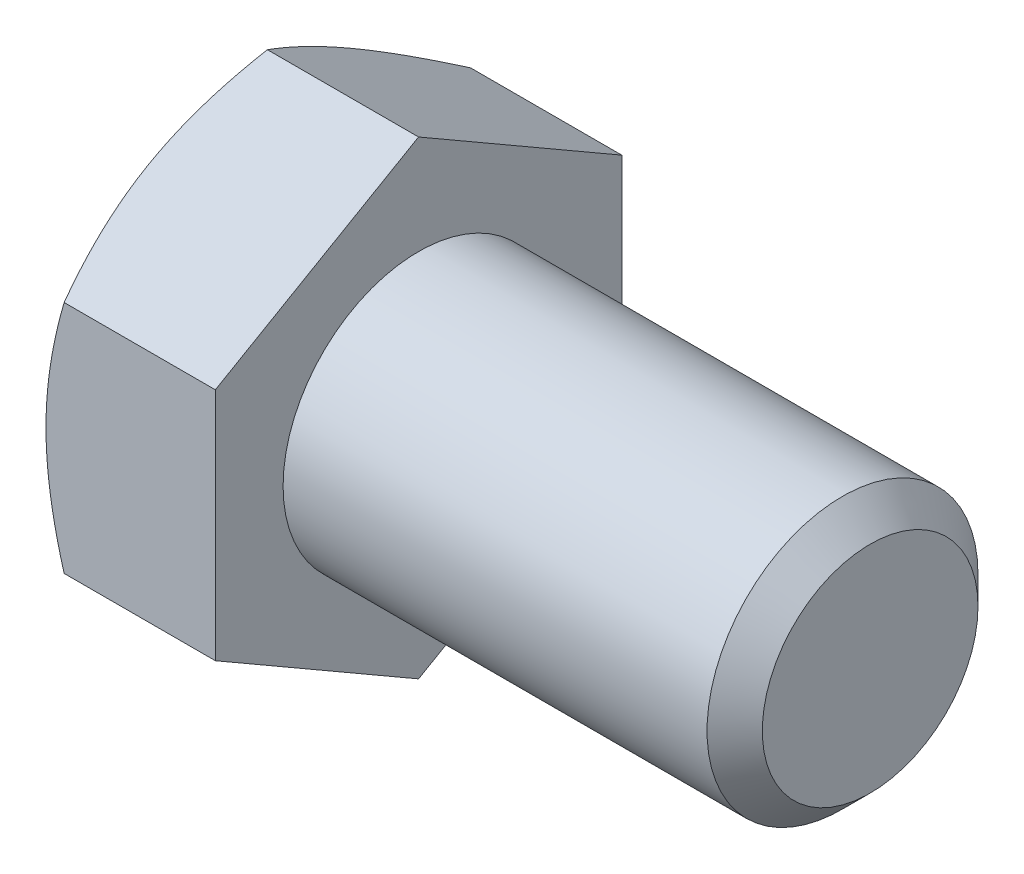
SolidWorks part; units mm, degrees
ref_plane "Front Plane" through (0, 0, 0) normal (0, 0, 1) x (1, 0, 0)
ref_plane "Top Plane" through (0, 0, 0) normal (0, 1, 0) x (1, 0, 0)
ref_plane "Right Plane" through (0, 0, 0) normal (1, 0, 0) x (0, 0, -1)
sketch "Sketch1" plane through (0, 0, 0) normal (0, 0, 1) x (1, 0, 0)
  line L0 (-10.9141, 0) -> (10.9141, 0) construction
  line L1 (10.9141, 4.7625) -> (10.9141, -4.7625) construction
  line L2 (-4.9609, 7.1437) -> (-4.9609, -7.1437) construction
  line L3 (-10.9141, 7.1437) -> (-10.9141, -7.1437) construction
  point P9 (-4.9609, 0)
  point P10 (5.3578, -4.7625)
  dimension "Screw Dia" = 9.525
  dimension "Hex" = 14.2875
  dimension "Head Ht" = 5.9531
  dimension "Screw Lenght" = 15.875
  dimension "D1" = 5.5562
ref_plane "Plane2" through (10.9141, 0, 0) normal (1, 0, 0) x (0, 0, -1)
sketch "Sketch5" plane through (10.9141, 0, 0) normal (1, 0, 0) x (0, 0, -1)
  circle A0 centre (0, 0) radius 4.7625
extrude "Boss-Extrude3" add sketch "Sketch5" against normal up to vertex (15.875 mm away) up to point (-4.9609, 0, 0)
sketch "Sketch9" plane through (10.9141, 0, 0) normal (1, 0, 0) x (0, 0, -1)
  circle A1 centre (0, 0) radius 4.7625
  circle A2 centre (0, 0) radius 4.7625
  dimension "D1" = 0
curve "Helix/Spiral1" pitch 1.5875 height 17.4625 turns 11 parameters "Pitch"=1.5875
chamfer "Chamfer1" distance 0.9715 angle 45 1 edges at (10.9141, 0, -4.7625)
sketch "Sketch10" plane through (0, 0, 0) normal (0, 0, 1) x (1, 0, 0)
  line L0 (10.9141, 4.7625) -> (11.5094, 3.7314)
  line L1 (11.5094, 3.7314) -> (11.7078, 3.7314)
  line L2 (11.7078, 3.7314) -> (12.3031, 4.7625)
  line L3 (10.9141, 4.7625) -> (12.3031, 4.7625)
  line L4 (11.6086, 4.7625) -> (11.6086, 3.7314) construction
  line L5 (11.2117, 4.2469) -> (12.0055, 4.2469) construction
  dimension "D1" = 60
  dimension "D2" = 0.1984
  dimension "D3" = 0.7937
sweep "Cut-Sweep1" [suppressed] cut profiles "Sketch10" path "Helix/Spiral1"
sketch "Sketch6" plane through (-4.9609, 0, 0) normal (-1, 0, 0) x (0, 0, 1)
  line L0 (0, 7.1437) -> (0, -7.1437) construction
  line L1 (7.1437, 4.1244) -> (0, 8.2489)
  line L2 (0, 8.2489) -> (-7.1438, 4.1244)
  line L3 (-7.1438, 4.1244) -> (-7.1438, -4.1244)
  line L4 (-7.1438, -4.1244) -> (0, -8.2489)
  line L5 (0, -8.2489) -> (7.1438, -4.1244)
  line L6 (7.1438, -4.1244) -> (7.1437, 4.1244)
  circle A0 centre (0, 0) radius 7.1438 construction
extrude "Boss-Extrude4" add sketch "Sketch6" along normal up to vertex (5.9531 mm away) up to point (-10.9141, -7.1437, 0)
sketch "Sketch7" plane through (-10.9141, 0, 0) normal (-1, 0, 0) x (0, 0, 1)
  circle A0 centre (0, 0) radius 7.1438 construction
  circle A1 centre (0, 0) radius 7.1438
sketch "Sketch8" plane through (-10.9141, 0, 0) normal (-1, 0, 0) x (0, 0, 1)
  circle A0 centre (0, 0) radius 7.1438 construction
  circle A1 centre (0, 0) radius 7.1438
extrude "Cut-Extrude3" cut sketch "Sketch8" against normal through all draft 60 flip side to cut
sketch "Sketch12" plane through (-10.9141, 0, 0) normal (-1, 0, 0) x (0, 0, 1)
  line L0 (0, 5.5007) -> (0, 3.0718) construction
  line L1 (0.2143, 5.5007) -> (0.2143, 3.0718)
  line L2 (-0.2143, 5.5007) -> (-0.2143, 3.0718)
  line L3 (0, 4.7625) -> (0, -4.7625) construction
  arc A0 (0.2143, 5.5007) -> (-0.2143, 5.5007) centre (0, 5.5007) ccw
  arc A1 (-0.2143, 3.0718) -> (0.2143, 3.0718) centre (0, 3.0718) ccw
  circle A3 centre (0, 0) radius 2.8575 construction
  circle A4 centre (0, 0) radius 5.715 construction
  point P2 (0, 4.2862)
  dimension "D1" = 5.715
  dimension "D3" = 11.43
  dimension "D2" = 0.4286
extrude "Cut-Extrude4" cut sketch "Sketch12" against normal blind 0.254
pattern_circular "CirPattern1" count 3 over 360 about axis through (-4.9609, 0, 0) along (1, 0, 0) of "Cut-Extrude4"
equation "\"D2@Sketch10\" = \"Pitch@Helix/Spiral1\"*.125"
equation "\"D3@Sketch10\" = \"Pitch@Helix/Spiral1\"*.5"
equation "\"D1@Chamfer1\" = \"Pitch@Helix/Spiral1\"*.612"
equation "\"D1@Sketch12\" = \"Hex@Sketch1\"*.4"
equation "\"D3@Sketch12\" = \"Hex@Sketch1\"*.8"
equation "\"D2@Sketch12\" = \"Hex@Sketch1\"*.03"
equation "\"D1@Sketch1\" = \"Pitch@Helix/Spiral1\"*3.5"
equation "\"D3@Helix/Spiral1\" = \"Screw Lenght@Sketch1\"+\"Pitch@Helix/Spiral1\""
